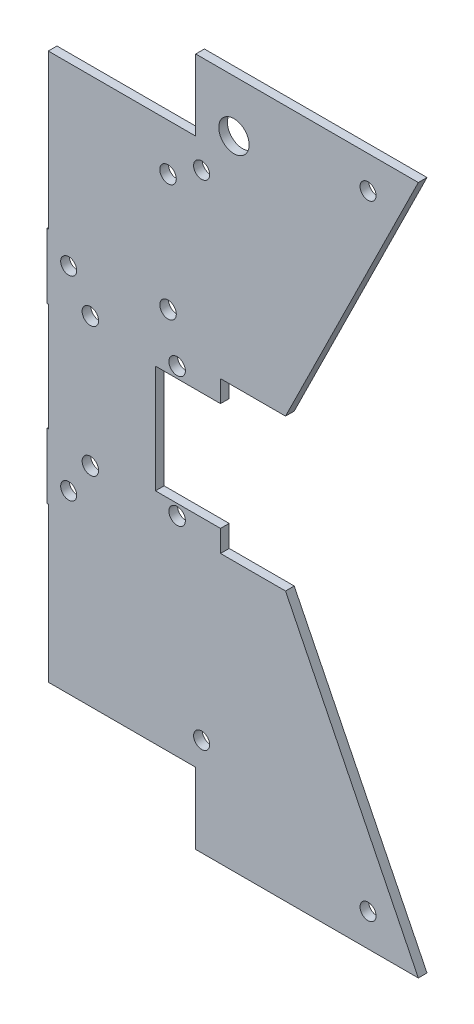
SolidWorks part; units mm, degrees
material "Thornel Mat VMA"
ref_plane "Front Plane" through (0, 0, 0) normal (0, 0, 1) x (1, 0, 0)
ref_plane "Top Plane" through (0, 0, 0) normal (0, 1, 0) x (1, 0, 0)
ref_plane "Right Plane" through (0, 0, 0) normal (1, 0, 0) x (0, 0, -1)
sketch "Sketch1" plane through (0, 0, 0) normal (0, 0, 1) x (1, 0, 0)
  line L0 (-2.9301, -104.5098) -> (-3.3149, -104.5098)
  line L1 (-3.3149, -72.8868) -> (-2.9301, -72.8868)
  line L78 (47.4851, -66.5368) -> (47.4851, -72.8868)
  line L79 (47.4851, -104.5098) -> (47.4851, -110.8598)
  line L80 (66.5174, -66.5368) -> (105.3971, 12.1397)
  line L81 (105.3971, 12.1397) -> (38.7094, 12.1397)
  line L88 (38.7094, 12.1397) -> (38.7094, -8.6883)
  line L89 (-2.9301, -8.6883) -> (38.7094, -8.6883)
  line L90 (-3.3149, -53.8368) -> (-2.9301, -53.8368)
  line L91 (-2.9301, -53.8368) -> (-2.9301, -8.6883)
  line L92 (-3.3149, -66.5368) -> (-3.3149, -53.8368)
  line L93 (-3.3149, -72.8868) -> (-3.3149, -66.5368)
  line L94 (-2.9301, -104.5098) -> (-2.9301, -72.8868)
  line L95 (-3.3149, -110.8598) -> (-3.3149, -104.5098)
  line L96 (66.5174, -110.8598) -> (105.3971, -189.5363)
  line L97 (105.3971, -189.5363) -> (38.7094, -189.5363)
  line L98 (38.7094, -189.5363) -> (38.7094, -168.7083)
  line L99 (-2.9301, -168.7083) -> (38.7094, -168.7083)
  line L106 (-3.3149, -110.8598) -> (-3.3149, -123.5598)
  line L107 (-3.3149, -123.5598) -> (-2.9301, -123.5598)
  line L108 (66.5174, -110.8598) -> (47.4851, -110.8598)
  line L109 (47.4851, -66.5368) -> (66.5174, -66.5368)
  line L110 (47.4851, -104.5098) -> (47.4851, -72.8868)
  line L111 (-2.9301, -123.5598) -> (-2.9301, -168.7083)
  circle A0 centre (90.6739, 2.6147) radius 2.3495
  circle A1 centre (41.9566, -16.4353) radius 2.3495
  circle A2 centre (3.0351, -60.1868) radius 2.3495
  circle A3 centre (3.0351, -117.2098) radius 2.3495
  circle A4 centre (41.9566, -160.9613) radius 2.3495
  circle A5 centre (90.6739, -180.0113) radius 2.3495
  circle A6 centre (51.4094, -3.1003) radius 4.445
  point P2 (90.6739, 2.6147)
  point P4 (41.9566, -16.4353)
  point P6 (3.0351, -60.1868)
  point P8 (3.0351, -117.2098)
  point P10 (41.9566, -160.9613)
  point P11 (90.6739, -180.0113)
  dimension "D2" = 4.699
  dimension "D5" = 8.89
  dimension "D1" = 66.6876
  dimension "D3" = 12.7
  dimension "D4" = 15.24
extrude "Boss-Extrude1" add sketch "Sketch1" along normal blind 2.54
sketch "Sketch2" plane through (0, 0, 2.54) normal (0, 0, 1) x (1, 0, 0)
  line L0 (-3.3149, -53.8368) -> (-3.3149, -72.8868) construction
  line L1 (47.4851, -66.5368) -> (66.5174, -66.5368) construction
  line L2 (47.4851, -88.6983) -> (-2.9301, -88.6983) construction
  line L3 (47.4851, -110.8598) -> (47.4851, -66.5368) construction
  line L4 (-2.9301, -72.8868) -> (-2.9301, -104.5098) construction
  circle A0 centre (9.3851, -69.7118) radius 2.413
  circle A2 centre (34.7851, -69.7118) radius 2.413
  circle A4 centre (34.7851, -107.6848) radius 2.413
  circle A6 centre (9.3851, -107.6848) radius 2.413
  point P2 (0, 0)
  point P3 (0, 0)
  dimension "D1" = 4.826
  dimension "D2" = 25.4
  dimension "D3" = 4.826
  dimension "D5" = 12.7
  dimension "D7" = 3.175
extrude "Cut-Extrude1" cut sketch "Sketch2" against normal through all
sketch "Sketch3" plane through (0, 0, 2.54) normal (0, 0, 1) x (1, 0, 0)
  line L0 (47.4851, -110.8598) -> (47.4851, -66.5368) construction
  line L1 (47.4851, -72.8868) -> (28.4351, -72.8868)
  line L2 (47.4851, -72.8868) -> (47.4851, -104.5098)
  line L3 (47.4851, -104.5098) -> (28.4351, -104.5098)
  line L4 (28.4351, -72.8868) -> (28.4351, -104.5098)
  line L5 (47.4851, -66.5368) -> (66.5174, -66.5368) construction
  line L6 (66.5174, -110.8598) -> (47.4851, -110.8598) construction
  circle A1 centre (9.3851, -69.7118) radius 2.413 construction
  dimension "D3" = 19.05
  dimension "D1" = 6.35
  dimension "D2" = 6.35
extrude "Cut-Extrude2" cut sketch "Sketch3" against normal through all
sketch "Sketch4" plane through (0, 0, 2.54) normal (0, 0, 1) x (1, 0, 0)
  line L0 (-2.9301, -168.7083) -> (38.7094, -168.7083) construction
  line L1 (27.4577, 15.7469) -> (40.2334, 15.7469)
  line L2 (27.4577, 15.7469) -> (27.4577, -8.6883)
  line L3 (27.4577, -8.6883) -> (40.2334, -8.6883)
  line L4 (40.2334, 15.7469) -> (40.2334, -8.6883)
  line L5 (0, -197.042) -> (40.2334, -197.042)
  line L6 (0, -197.042) -> (0, -168.7083)
  line L7 (0, -168.7083) -> (40.2334, -168.7083)
  line L8 (40.2334, -197.042) -> (40.2334, -168.7083)
  line L9 (38.7094, -168.7083) -> (38.7094, -189.5363) construction
  line L10 (38.7094, -8.6883) -> (-2.9301, -8.6883) construction
  dimension "D1" = 1.524
extrude "Cut-Extrude3" cut sketch "Sketch4" against normal through all
sketch "Sketch5" plane through (0, 0, 0) normal (0, 0, -1) x (-1, 0, 0)
  line L0 (2.9301, -8.6883) -> (2.9301, -53.8368) construction
  line L1 (-40.2334, -8.6883) -> (2.9301, -8.6883) construction
  circle A0 centre (-32.1219, -22.4043) radius 2.413
  circle A1 centre (-32.1219, -56.6943) radius 2.413
  point P8 (0, 0)
  dimension "D4" = 4.826
  dimension "D1" = 35.052
  dimension "D2" = 13.716
  dimension "D3" = 34.29
extrude "Cut-Extrude4" cut sketch "Sketch5" against normal through all
